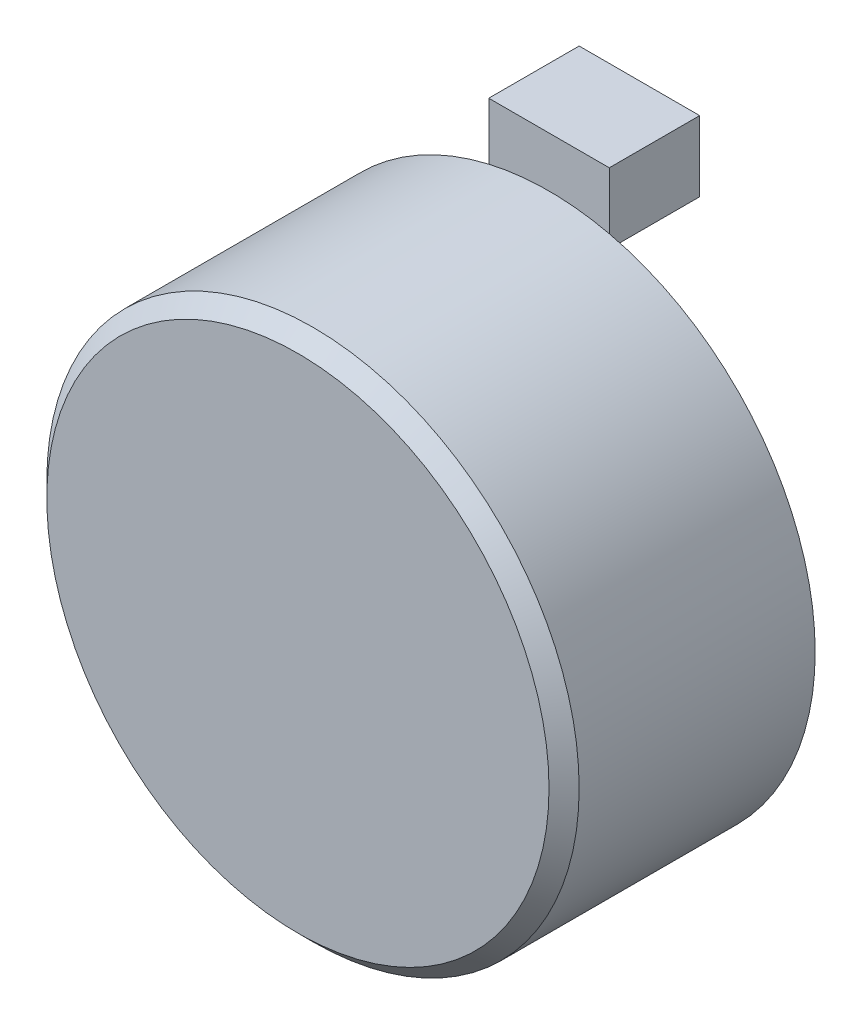
SolidWorks part; units mm, degrees
ref_plane "Front Plane" through (0, 0, 0) normal (0, 0, 1) x (1, 0, 0)
ref_plane "Top Plane" through (0, 0, 0) normal (0, 1, 0) x (1, 0, 0)
ref_plane "Right Plane" through (0, 0, 0) normal (1, 0, 0) x (0, 0, -1)
sketch "SK_Body" plane through (0, 0, 0) normal (0, 1, 0) x (1, 0, 0)
  line L0 (0, -10) -> (0, 60) construction
  line L1 (0, 0) -> (50, 0)
  line L2 (50, 0) -> (53, 3)
  line L3 (53, 3) -> (53, 50)
  line L4 (53, 50) -> (50, 50)
  line L5 (50, 50) -> (0, 50)
  line L6 (0, 50) -> (0, 0)
  dimension "P1" = 10
  dimension "P2" = 60
  dimension "R_front" = 50
  dimension "P4" = 53
  dimension "P5" = 3
  dimension "R_body" = 53
  dimension "L_body" = 50
  dimension "P8" = 50
  dimension "P9" = 50
  dimension "P10" = 50
revolve "Housing_Body" add sketch "SK_Body" angle 360 about L0
ref_plane "PL_Rear" through (0, 0, -50) normal (0, 0, 1) x (1, 0, 0)
sketch "SK_RearHole" plane through (0, 0, -50) normal (0, 0, 1) x (1, 0, 0)
  circle A0 centre (45, 0) radius 1.65
  dimension "D_rh" = 3.3
  dimension "R_rh" = 45
extrude "Rear_Tapped_Hole" cut sketch "SK_RearHole" along normal blind 8
ref_axis "AX_Joint" through (0, 0, -71.4) along (0, 0, 1)
pattern_circular "Rear_Hole_Pattern" count 8 over 360 about axis through (0, 0, -71.4) along (0, 0, 1) of "Rear_Tapped_Hole"
sketch "SK_Connector" plane through (0, 0, -50) normal (0, 0, 1) x (1, 0, 0)
  line L0 (-12, 49) -> (12, 49)
  line L1 (12, 49) -> (12, 63)
  line L2 (12, 63) -> (-12, 63)
  line L3 (-12, 63) -> (-12, 49)
  dimension "P1" = 12
  dimension "P2" = 49
  dimension "P3" = 12
  dimension "P4" = 49
  dimension "P5" = 12
  dimension "P6" = 63
  dimension "P7" = 12
  dimension "P8" = 63
extrude "Connector_Zone" add sketch "SK_Connector" against normal blind 18
equation "\"D_act\" = 106"
equation "\"L_housing\" = 50"
equation "\"PCD_rear\" = 90"
equation "\"D_rear_hole\" = 3.3"
equation "\"D_bearing_boss\" = 64"
equation "\"R_front@SK_Body\" = \"D_act\"/2-3.0"
equation "\"R_body@SK_Body\" = \"D_act\"/2"
equation "\"L_body@SK_Body\" = \"L_housing\""
equation "\"D_rh@SK_RearHole\" = \"D_rear_hole\""
equation "\"R_rh@SK_RearHole\" = \"PCD_rear\"/2"
